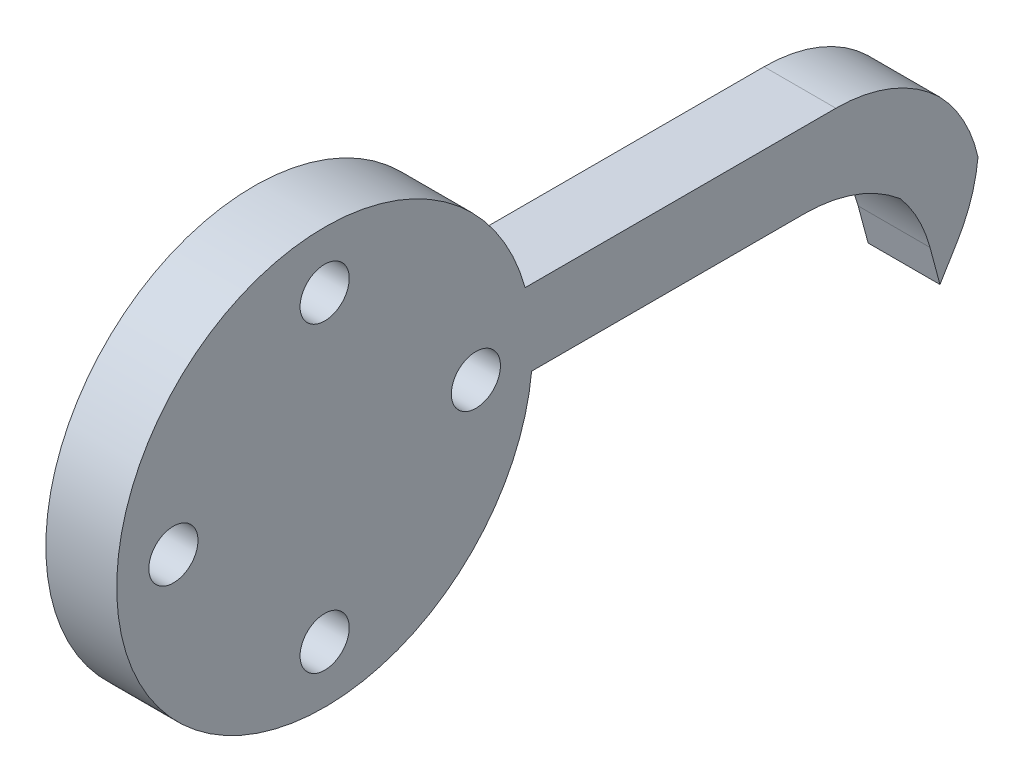
SolidWorks part; units mm, degrees
ref_plane "Front Plane" through (0, 0, 0) normal (0, 0, 1) x (1, 0, 0)
ref_plane "Top Plane" through (0, 0, 0) normal (0, 1, 0) x (1, 0, 0)
ref_plane "Right Plane" through (0, 0, 0) normal (1, 0, 0) x (0, 0, -1)
sketch "Sketch1" plane through (0, 0, 0) normal (1, 0, 0) x (0, 0, -1)
  circle A0 centre (0, 0) radius 13.97
  circle A1 centre (-10.16, 0) radius 1.651
  circle A2 centre (0, 10.16) radius 1.651
  circle A3 centre (10.16, 0) radius 1.651
  circle A4 centre (0, -10.16) radius 1.651
  point P14 (0, 0)
  dimension "D1" = 27.94
  dimension "D2" = 3.302
  dimension "D4" = 4
  dimension "D3" = 10.16
extrude "Boss-Extrude1" add sketch "Sketch1" along normal blind 4.7625
sketch "Sketch2" plane through (4.7625, 0, 0) normal (1, 0, 0) x (0, 0, -1)
  line L0 (13.4673, 3.714) -> (38.4863, 3.714)
  line L1 (13.9031, -1.366) -> (36.3821, -1.366)
  line L2 (38.4863, 3.714) -> (43.8744, -1.6742)
  line L3 (36.3821, -1.366) -> (39.9742, -4.9581)
  line L4 (39.9742, -4.9581) -> (41.3353, -10.0381)
  line L5 (43.8744, -1.6742) -> (44.1126, -5.4842)
  line L6 (44.1126, -5.4842) -> (41.3353, -10.0381)
  line L7 (13.4673, 3.714) -> (12.4565, 3.714)
  line L8 (12.4565, 3.714) -> (12.4565, -1.366)
  line L9 (12.4565, -1.366) -> (13.9031, -1.366)
  circle A1 centre (0, 0) radius 13.97 construction
  circle A2 centre (10.16, 0) radius 1.651 construction
  dimension "D13" = 2.2965
  dimension "D2" = 25.019
  dimension "D3" = 5.08
  dimension "D4" = 22.479
  dimension "D5" = 45
  dimension "D6" = 7.62
  dimension "D7" = 5.08
  dimension "D8" = 5.08
  dimension "D9" = 5.08
  dimension "D10" = 30
  dimension "D11" = 5.334
  dimension "D12" = 3.81
extrude "leg1" add sketch "Sketch2" against normal blind 4.826
fillet "Fillet2" radius 10 5 edges at (2.3495, -4.9581, -39.9742) (2.3495, -1.366, -36.3821) (2.3495, 3.714, -38.4863) (2.3495, -1.6742, -43.8744) (2.3495, -5.4842, -44.1126)
